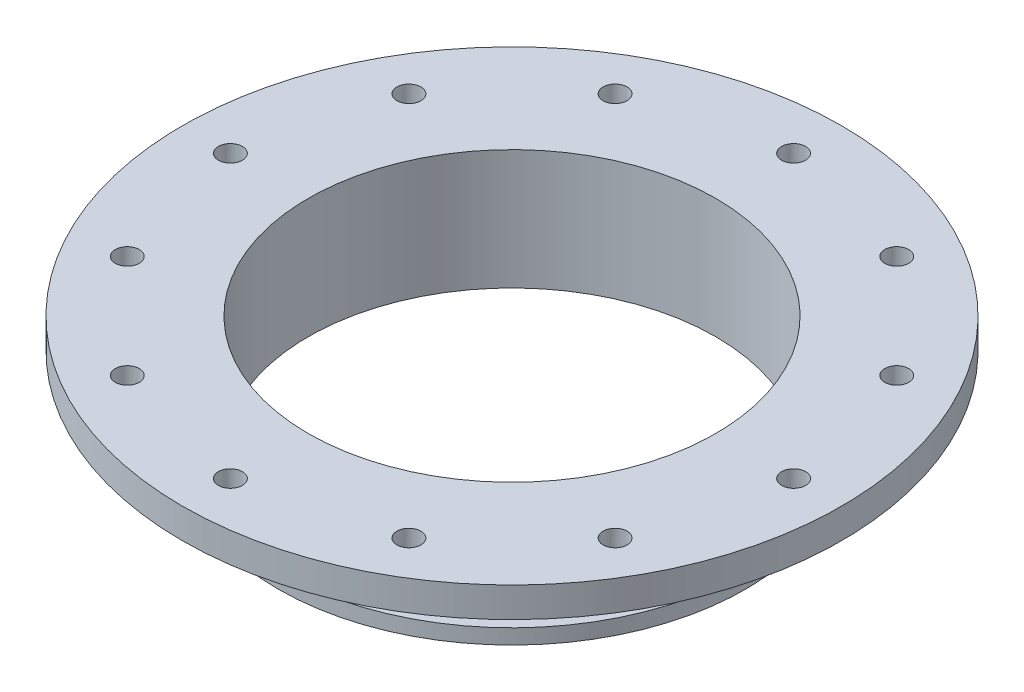
SolidWorks part; units mm, degrees
material "1023 Carbon Steel Sheet (SS)"
ref_plane "Front Plane" through (0, 0, 0) normal (0, 0, 1) x (1, 0, 0)
ref_plane "Top Plane" through (0, 0, 0) normal (0, 1, 0) x (1, 0, 0)
ref_plane "Right Plane" through (0, 0, 0) normal (1, 0, 0) x (0, 0, -1)
sketch "Sketch1" plane through (0, 0, 0) normal (0, 0, 1) x (1, 0, 0)
  line L0 (-43.18, 0) -> (43.18, 0) construction
  line L1 (0, -127) -> (0, 127) construction
  line L2 (43.18, 0) -> (43.18, -6.35)
  line L4 (43.18, 0) -> (69.85, 0)
  line L6 (43.18, -6.35) -> (69.85, -6.35)
  line L7 (69.85, -6.35) -> (69.85, 0)
  point P4 (0, 0)
  point P8 (0, 0)
  dimension "D1" = 86.36
  dimension "D2" = 254
  dimension "D3" = 6.35
  dimension "D4" = 26.67
revolve "Revolve1" add sketch "Sketch1" angle 360 about L1
sketch "Sketch2" plane through (0, -6.35, 0) normal (0, -1, 0) x (1, 0, 0)
  circle A0 centre (0, 0) radius 43.18
  circle A1 centre (0, 0) radius 43.18 construction
  circle A2 centre (0, 0) radius 49.53
  dimension "D1" = 6.35
extrude "Boss-Extrude1" add sketch "Sketch2" along normal blind 19.05
sketch "Sketch3" plane through (0, 0, 0) normal (0, 0, 1) x (1, 0, 0)
  line L0 (0, 0) -> (0, -37.1244) construction
  line L1 (49.53, -25.4) -> (49.53, -6.35) construction
  line L2 (-49.53, -25.4) -> (49.53, -25.4) construction
  line L3 (-49.53, -6.35) -> (49.53, -6.35) construction
  line L5 (49.53, -25.4) -> (46.355, -25.4)
  line L6 (49.53, -25.4) -> (49.53, -6.35) construction
  line L7 (49.53, -6.35) -> (46.355, -6.35)
  line L8 (46.355, -25.4) -> (46.355, -6.35)
  line L9 (49.53, -22.225) -> (46.355, -22.225)
  line L10 (49.53, -22.225) -> (49.53, -20.1083)
  line L11 (49.53, -20.1083) -> (46.355, -20.1083)
  line L12 (46.355, -22.225) -> (46.355, -20.1083)
  line L13 (49.53, -16.9333) -> (46.355, -16.9333)
  line L14 (49.53, -16.9333) -> (49.53, -14.8167)
  line L15 (49.53, -14.8167) -> (46.355, -14.8167)
  line L16 (46.355, -16.9333) -> (46.355, -14.8167)
  line L17 (49.53, -11.6417) -> (46.355, -11.6417)
  line L18 (49.53, -11.6417) -> (49.53, -9.525)
  line L19 (49.53, -9.525) -> (46.355, -9.525)
  line L20 (46.355, -11.6417) -> (46.355, -9.525)
  dimension "D1" = 3.175
  dimension "D2" = 3.175
  dimension "D3" = 3.175
  dimension "D4" = 3.175
  dimension "D5" = 3.175
revolve "Cut-Revolve1" cut sketch "Sketch3" angle 360 about L0 region at (47.9425, -10.5833, 0) region at (47.9425, -15.875, 0) region at (47.9425, -21.1667, 0)
sketch "Sketch4" plane through (0, 0, 0) normal (0, 1, 0) x (1, 0, 0)
  line L0 (0, 0) -> (-49.53, 0)
  line L1 (-49.53, 0) -> (-59.69, 0)
  circle A0 centre (0, 0) radius 49.53 construction
  circle A1 centre (-59.69, 0) radius 2.54
  dimension "D2" = 5.08
  dimension "D1" = 10.16
extrude "Cut-Extrude1" cut sketch "Sketch4" against normal through all contours A1 region at (-62.1582, 0, 0)
pattern_circular "CirPattern1" count 12 over 360 about axis through (0, 0, 0) along (0, -1, 0) of "Cut-Extrude1"
sketch "point" plane through (0, 0, 0) normal (0, 1, 0) x (1, 0, 0)
  point P0 (0, 0)
equation "\"D3@Sketch3\"=\"D2@Sketch3\""
equation "\"D4@Sketch3\"=\"D2@Sketch3\""
equation "\"D5@Sketch3\"=\"D2@Sketch3\""
